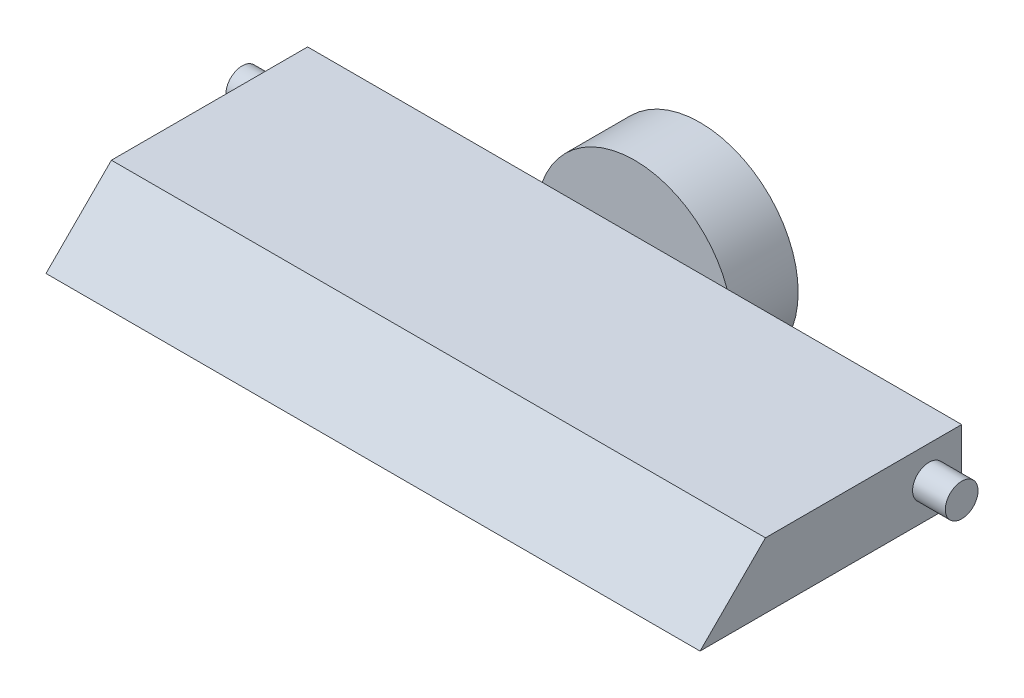
SolidWorks part; units mm, degrees
ref_plane "Front Plane" through (0, 0, 0) normal (0, 0, 1) x (1, 0, 0)
ref_plane "Top Plane" through (0, 0, 0) normal (0, 1, 0) x (1, 0, 0)
ref_plane "Right Plane" through (0, 0, 0) normal (1, 0, 0) x (0, 0, -1)
sketch "Sketch2" plane through (0, 0, -146.6111) normal (0, 0, 1) x (1, 0, 0)
  line L10 (-53.541, -150.9549) -> (-33.541, -150.9549)
  line L11 (-33.541, -150.9549) -> (-33.541, -148.9549)
  line L12 (-33.541, -148.9549) -> (-53.541, -148.9549)
  line L13 (-53.541, -148.9549) -> (-53.541, -150.9549)
  dimension "D1" = 27.2582
  dimension "D2" = 47.2582
  dimension "D3" = 44.9944
  dimension "D4" = 46.9944
extrude "Boss-Extrude1" add sketch "Sketch2" along normal blind 4 and the other way blind 4 contours L10 L11 L12 L13
sketch "Sketch4" plane through (-53.541, 0, 0) normal (-1, 0, 0) x (0, 0, 1)
  line L0 (-142.6111, -148.9549) -> (-142.6111, -150.9549)
  line L1 (-142.6111, -148.9549) -> (-144.6111, -148.9549)
  line L2 (-150.6111, -148.9549) -> (-142.6111, -148.9549) construction
  line L3 (-142.6111, -150.9549) -> (-144.6111, -148.9549)
  dimension "D1" = 2
extrude "Cut-Extrude1" cut sketch "Sketch4" against normal up to surface (20 mm away) up to face at (-33.541, -149.9549, -146.6111)
sketch "Sketch5" plane through (-53.541, 0, 0) normal (-1, 0, 0) x (0, 0, 1)
  arc A1 (-149.6111, -150.4549) -> (-149.6111, -149.4549) centre (-149.6111, -149.9549) ccw construction
  circle A3 centre (-149.6111, -149.9549) radius 0.5
  point P5 (-149.6111, -149.9549)
extrude "Boss-Extrude3" add sketch "Sketch5" along normal blind 1
ref_plane "Plane1" through (-43.541, 0, 0) normal (-1, 0, 0) x (0, 0, 1)
mirror "Mirror2" about plane through (-43.541, 0, 0) normal (-1, 0, 0) of "Boss-Extrude3"
sketch "Sketch6" plane through (0, 0, 0) normal (0, 0, 1) x (1, 0, 0)
  circle A0 centre (0, 0) radius 2.5
  circle A1 centre (2.5, 0) radius 0.25
sketch "Sketch7" plane through (0, 0, -218.6111) normal (0, 0, 1) x (1, 0, 0)
  circle A2 centre (-43.541, -149.9549) radius 3
sketch "Sketch8" plane through (0, 0, -150.6111) normal (0, 0, -1) x (-1, 0, 0)
  circle A1 centre (43.541, -149.9549) radius 3
  circle A2 centre (43.541, -149.9549) radius 3
  dimension "D1" = 0
extrude "Boss-Extrude5" add sketch "Sketch8" along normal blind 2
